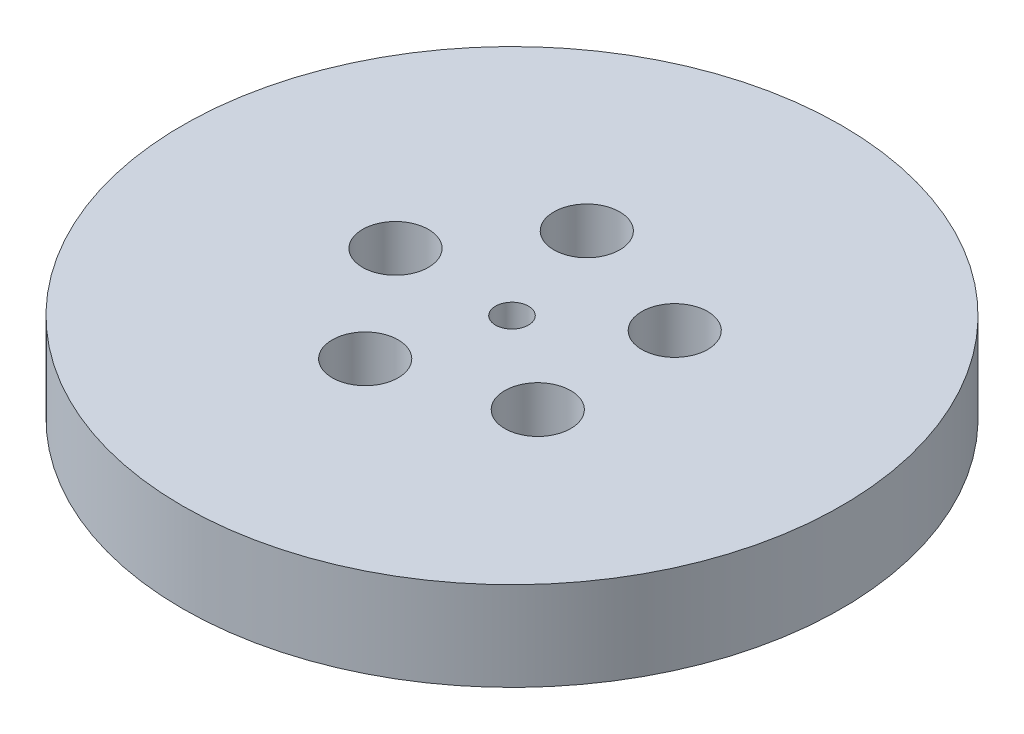
SolidWorks part; units mm, degrees
ref_plane "Front Plane" through (0, 0, 0) normal (0, 0, 1) x (1, 0, 0)
ref_plane "Top Plane" through (0, 0, 0) normal (0, 1, 0) x (1, 0, 0)
ref_plane "Right Plane" through (0, 0, 0) normal (1, 0, 0) x (0, 0, -1)
sketch "Sketch1" plane through (0, 0, 0) normal (0, 1, 0) x (1, 0, 0)
  circle A0 centre (0, 0) radius 100
  dimension "FLANGE_OD" = 200
extrude "Boss-Extrude1" add sketch "Sketch1" along normal blind 27
sketch "Sketch2" plane through (0, 0, 0) normal (0, 1, 0) x (1, 0, 0)
  circle A0 centre (0, 0) radius 5
  dimension "BORE_D" = 10
extrude "Cut-Extrude1" cut sketch "Sketch2" along normal through all
sketch "Sketch3" plane through (0, 27, 0) normal (0, 1, 0) x (1, 0, 0)
  circle A0 centre (0, 0) radius 35.3511 construction
  circle A1 centre (-35.3511, 0) radius 10
  dimension "BOLT_D" = 20
  dimension "BOLT_PCD" = 70.7023
extrude "Cut-Extrude2" cut sketch "Sketch3" against normal blind 22.8003
pattern_circular "CirPattern1" count 5 over 360 about axis through (0, 0, 0) along (0, 1, 0) of "Cut-Extrude2"
